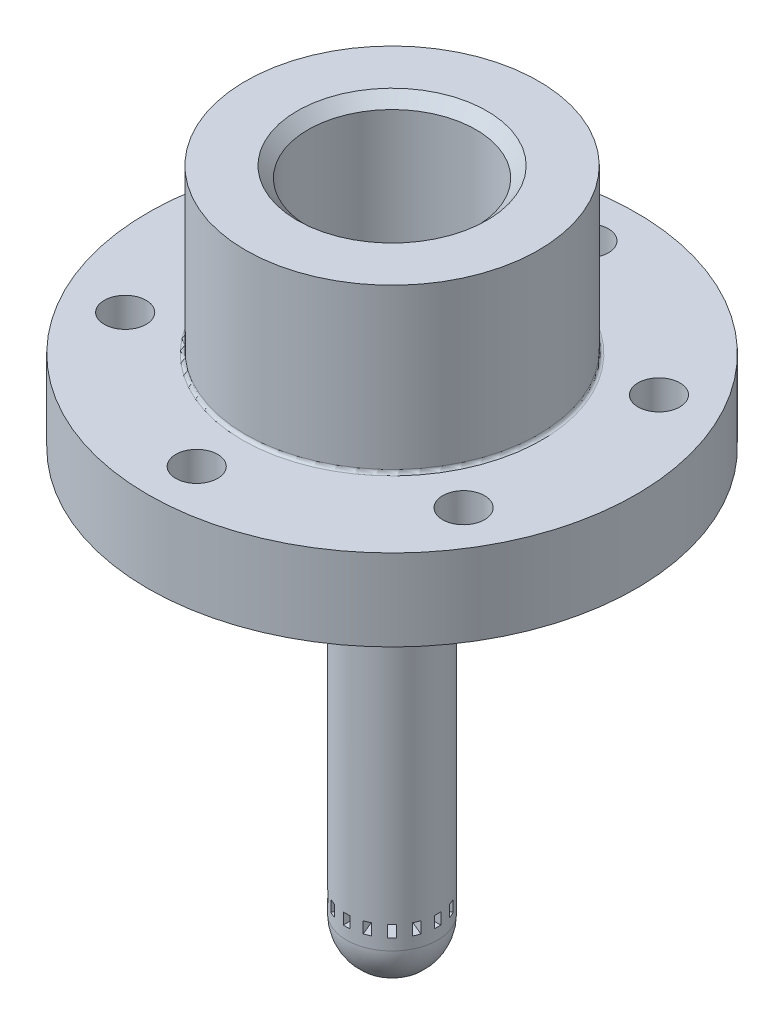
SolidWorks part; units mm, degrees
note: '?' marks a value the reader was unsure of.
ref_plane "Front Plane" through (0, 0, 0) normal (0, 0, 1) x (1, 0, 0)
ref_plane "Top Plane" through (0, 0, 0) normal (0, 1, 0) x (1, 0, 0)
ref_plane "Right Plane" through (0, 0, 0) normal (1, 0, 0) x (0, 0, -1)
sketch "Sketch1" plane through (0, 0, 0) normal (0, 0, 1) x (1, 0, 0)
  line L0 (-3.556, -2.0672) -> (-1.524, -2.0672) construction
  line L1 (0, 8.2157) -> (0, -2.0672) construction
  line L2 (-3.556, 23.0788) -> (-1.524, 23.0788)
  line L3 (-3.556, -2.0672) -> (-3.556, 23.0788)
  line L5 (0, -1.6066) -> (0, -5.6232)
  line L7 (-1.524, 23.0788) -> (-1.524, -2.0672)
  arc A0 (-1.524, -2.0672) -> (0, -1.6066) centre (-1.3783, 0.2022) ccw
  arc A2 (-3.556, -2.0672) -> (0, -5.6232) centre (0, -2.0672) ccw
  dimension "D1" = 3.556
  dimension "D2" = 3.556
  dimension "D3" = 1.524
  dimension "D4" = 25.146
revolve "Revolve2" add sketch "Sketch1" angle 360 about L1
ref_plane "Plane1" through (-3.556, 0, 0) normal (-1, 0, 0) x (0, 0, 1)
sketch "Sketch2" plane through (-3.556, 0, 0) normal (-1, 0, 0) x (0, 0, 1)
  line L0 (0.2542, -1.1782) -> (-0.2538, -1.1782)
  line L1 (-0.2538, -1.1782) -> (-0.2538, -0.2892)
  line L2 (-0.2538, -0.2892) -> (0.2542, -0.2892)
  line L3 (0.2542, -0.2892) -> (0.2542, -1.1782)
  line L4 (3.556, -2.0672) -> (-3.556, -2.0672) construction
  dimension "D2" = 0.508
  dimension "D1" = 0.889
  dimension "D3" = 0.889
extrude "Cut-Extrude1" cut sketch "Sketch2" along normal up to surface (2.0534 mm away)
pattern_circular "CirPattern1" count 16 over 360 about axis through (0, 0, 0) along (0, 1, 0) of "Cut-Extrude1"
ref_plane "Plane2" through (0, 23.0788, 0) normal (0, -1, 0) x (-1, 0, 0)
sketch "Sketch3" plane through (0, 23.0788, 0) normal (0, -1, 0) x (-1, 0, 0)
  circle A1 centre (0, 0) radius 1.524
  circle A2 centre (0, 0) radius 3.556
  dimension "D1" = 3.048
extrude "Boss-Extrude1" add sketch "Sketch3" against normal blind 6.35
ref_plane "Plane3" through (0, 29.4288, 0) normal (0, 1, 0) x (1, 0, 0)
sketch "Sketch4" plane through (0, 29.4288, 0) normal (0, 1, 0) x (1, 0, 0)
  circle A0 centre (0, 0) radius 19.05
  circle A1 centre (0, 0) radius 1.524
extrude "Boss-Extrude2" add sketch "Sketch4" along normal blind 6.35
sketch "Sketch11" plane through (0, 35.7788, 0) normal (0, 1, 0) x (1, 0, 0)
  line L0 (0, 0) -> (0, -15.24) construction
  circle A0 centre (0, -15.24) radius 1.6319
  circle A1 centre (0, 0) radius 15.24 construction
  dimension "D2" = 3.2639
extrude "Cut-Extrude2" cut sketch "Sketch11" against normal up to next
ref_axis "Axis1" through (0, -2.0672, 0) along (0, 1, 0)?
pattern_circular "CirPattern2" count 6 over 360 about axis through (0, 0, 0) along (0, 1, 0) of "Cut-Extrude2"
chamfer "Chamfer1" distance 3.048 angle 60 1 edges at (0, 35.7788, 1.524)
sketch "Sketch13" plane through (0, 35.7788, 0) normal (0, 1, 0) x (1, 0, 0)
  circle A0 centre (0, 0) radius 6.5481
  circle A1 centre (0, 0) radius 11.43
extrude "Boss-Extrude4" add sketch "Sketch13" along normal blind 12.7
fillet "Fillet4" radius 0.254 1 edges at (0, 35.7788, 11.43)
chamfer "Chamfer2" distance 0.8517 distance2 0.8395 1 edges at (0, 48.4788, 6.5481)
sketch "Sketch14" plane through (0, 35.7788, 0) normal (0, 1, 0) x (1, 0, 0)
  circle A0 centre (-13.1982, -7.62) radius 2.794
equation "\"ManifoldThickness\"= 0.250"
equation "\"D1@Boss-Extrude1\"=\"ManifoldThickness\""
equation "\"SkipDistance\"= \"OD\"'equal to pintle OD"
equation "\"OD\"= 0.280"
equation "\"AnnulusLength\"= 0.29"
equation "\"ManifoldChamberThickness\"= 0.35"
equation "\"D4@Sketch1\"=\"SkipDistance\"+\"AnnulusLength\"+\"ManifoldChamberThickness\"+\"HoleHeight\"+\"WeldHeight\""
equation "\"HoleHeight\"= 0.035"
equation "\"D2@Sketch1\"=\"OD\"/2"
equation "\"IR\"=0.06"
equation "\"D3@Sketch1\" = \"IR\""
equation "\"D1@Sketch3\"=\"ID\""
equation "\"ID\"= \"IR\" * 2"
equation "\"440loose\"= 0.1285"
equation "\"D2@Sketch11\"=\"440loose\""
equation "\"ManifoldPlateThickness\"= 0.25"
equation "\"WeldHeight\"= 0.035"
equation "\"D1@Sketch2\"=\"HoleHeight\""
equation "\"D3@Sketch2\"=\"WeldHeight\""
